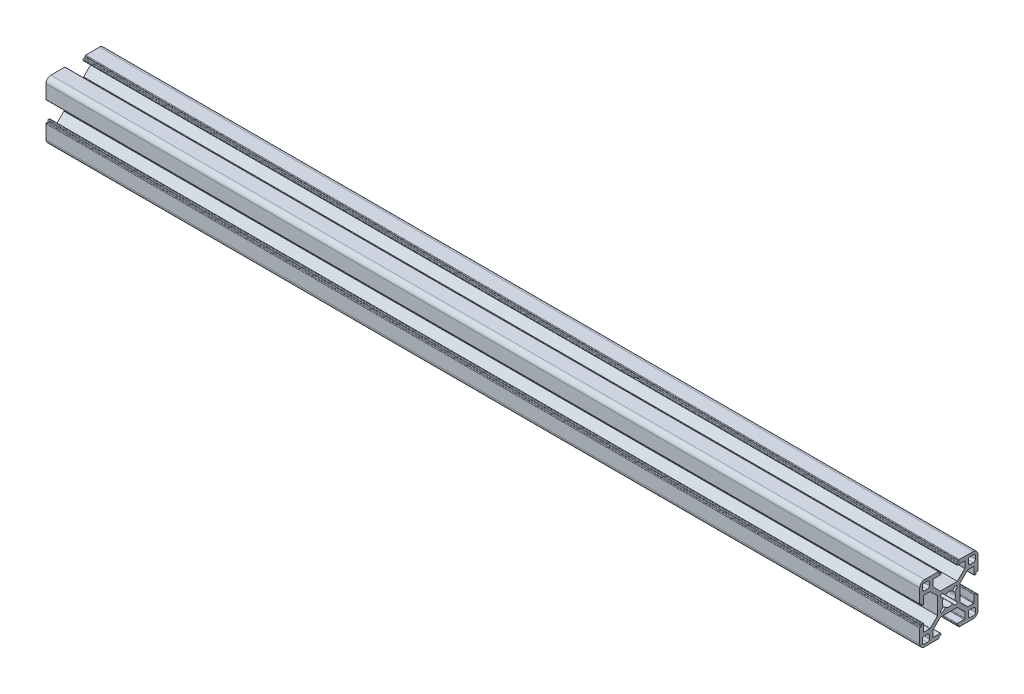
SolidWorks part; units mm, degrees
material "2.0966 (CuAl10Ni5Fe4)"
ref_plane "Front Plane" through (0, 0, 0) normal (0, 0, 1) x (1, 0, 0)
ref_plane "Top Plane" through (0, 0, 0) normal (0, 1, 0) x (1, 0, 0)
ref_plane "Right Plane" through (0, 0, 0) normal (1, 0, 0) x (0, 0, -1)
ref_axis "Axis_X" through (-58.3, 0, 0) along (1, 0, 0)
ref_axis "Axis_Y" through (0, 38.5, 0) along (0, -1, 0)
ref_axis "Axis_Z" through (0, 0, -4.5) along (0, 0, 1)
sketch "Sketch2" plane through (0, 0, 0) normal (1, 0, 0) x (0, 0, -1)
  line L1 (-15, 15) -> (15, 15)
  line L2 (-15, 15) -> (-15, -15)
  line L3 (-15, -15) -> (15, -15)
  line L4 (15, 15) -> (15, -15)
  line L5 (-15, 15) -> (15, -15) construction
  line L6 (-15, -15) -> (15, 15) construction
  point P0 (0, 0)
  dimension "D1" = 30
  dimension "D2" = 30
extrude "Boss-Extrude1" add sketch "Sketch2" along normal blind 450
sketch "Sketch5" plane through (450, 0, 0) normal (1, 0, 0) x (0, 0, -1)
  circle A0 centre (0, 0) radius 3.4
  dimension "D1" = 6.8
extrude "Cut-Extrude2" cut sketch "Sketch5" against normal through all
sketch "Sketch4" plane through (450, 0, 0) normal (1, 0, 0) x (0, 0, -1)
  line L0 (-4.3858, -5.8) -> (4.3858, -5.8)
  line L1 (4.3858, -5.8) -> (8.1621, -9.5763)
  line L2 (8.25, -9.7885) -> (8.25, -13)
  line L3 (8.25, -13) -> (4.1, -13)
  line L4 (4.1, -13) -> (4.1, -14)
  line L5 (4.1, -14) -> (5.1, -14)
  line L6 (5.1, -14) -> (5.1, -15)
  line L7 (-15, -15) -> (15, -15) construction
  line L8 (5.1, -15) -> (-5.1, -15)
  line L9 (-5.1, -15) -> (-5.1, -14)
  line L10 (-5.1, -14) -> (-4.1, -14)
  line L11 (-4.1, -14) -> (-4.1, -13)
  line L12 (-4.1, -13) -> (-8.25, -13)
  line L13 (-8.25, -13) -> (-8.25, -9.7885)
  line L14 (-8.1621, -9.5763) -> (-4.3858, -5.8)
  line L16 (-4.1, -13) -> (4.1, -13) construction
  line L17 (0, -14) -> (0, -15) construction
  line L18 (-4.1, -14) -> (4.1, -14) construction
  line L19 (0, -5.8) -> (0, -13) construction
  line L20 (0, -13) -> (0, -14) construction
  line L21 (15, -15) -> (15, 15) construction
  line L22 (11.05, -10.05) -> (12.65, -10.05)
  line L23 (10.05, -11.05) -> (10.05, -12.65)
  line L24 (11.05, -13.65) -> (12.65, -13.65)
  line L25 (13.65, -11.05) -> (13.65, -12.65)
  line L26 (10.05, -10.05) -> (13.65, -13.65) construction
  line L27 (10.05, -13.65) -> (13.65, -10.05) construction
  line L28 (0, 0) -> (3.5355, -3.5355) construction
  line L29 (15, -15) -> (15, 15) construction
  line L30 (4.0659, -3.0052) -> (2.8753, -1.8146)
  line L31 (3.0052, -4.0659) -> (1.8146, -2.8753)
  arc A0 (12.65, -13.65) -> (13.65, -12.65) centre (12.65, -12.65) ccw
  arc A1 (11.05, -13.65) -> (10.05, -12.65) centre (11.05, -12.65) cw
  arc A2 (10.05, -11.05) -> (11.05, -10.05) centre (11.05, -11.05) cw
  arc A3 (12.65, -10.05) -> (13.65, -11.05) centre (12.65, -11.05) cw
  arc A4 (3.0052, -4.0659) -> (4.0659, -3.0052) centre (3.5355, -3.5355) ccw
  circle A5 centre (0, 0) radius 3.4 construction
  arc A6 (1.8146, -2.8753) -> (2.8753, -1.8146) centre (0, 0) ccw
  arc A7 (-8.25, -9.7885) -> (-8.1621, -9.5763) centre (-7.95, -9.7885) cw
  arc A8 (8.25, -9.7885) -> (8.1621, -9.5763) centre (7.95, -9.7885) ccw
  point P18 (11.85, -11.85)
  point P47 (-8.25, -9.6642)
  point P55 (8.25, -9.6642)
  dimension "D11" = 1
  dimension "D14" = 1.5
  dimension "D2" = 0.3
  dimension "D1" = 9.2
  dimension "D3" = 1
  dimension "D4" = 8.2
  dimension "D5" = 10.2
  dimension "D6" = 16.5
  dimension "D7" = 2
  dimension "D8" = 1.35
  dimension "D9" = 1.35
  dimension "D10" = 3.6
  dimension "D12" = 45
  dimension "D13" = 5
  dimension "D15" = 5.4237
extrude "Cut-Extrude1" cut sketch "Sketch4" against normal through all
fillet "Fillet1" radius 2.5 1 edges at (225, -15, -15)
fillet "Fillet2" radius 0.3 10 edges at (225, -14, -5.1) (225, -15, -5.1) (225, -14, -4.1) (225, -13, -4.1) (225, -13, -8.25) (225, -13, 8.25) (225, -13, 4.1) (225, -14, 4.1) (225, -14, 5.1) (225, -15, 5.1)
pattern_circular "CirPattern1" count 4 over 360 about axis through (0, 0, 0) along (1, 0, 0) of "Cut-Extrude1", "Fillet1", "Fillet2"
sketch "草图1" plane through (0, 5.8, 0) normal (0, 1, 0) x (1, 0, 0)
  circle A0 centre (285.2904, 0) radius 4.4
extrude "切除-拉伸1" cut sketch "草图1" against normal through all and the other way blind 10
equation "\"Factor\"= 1.082532"
